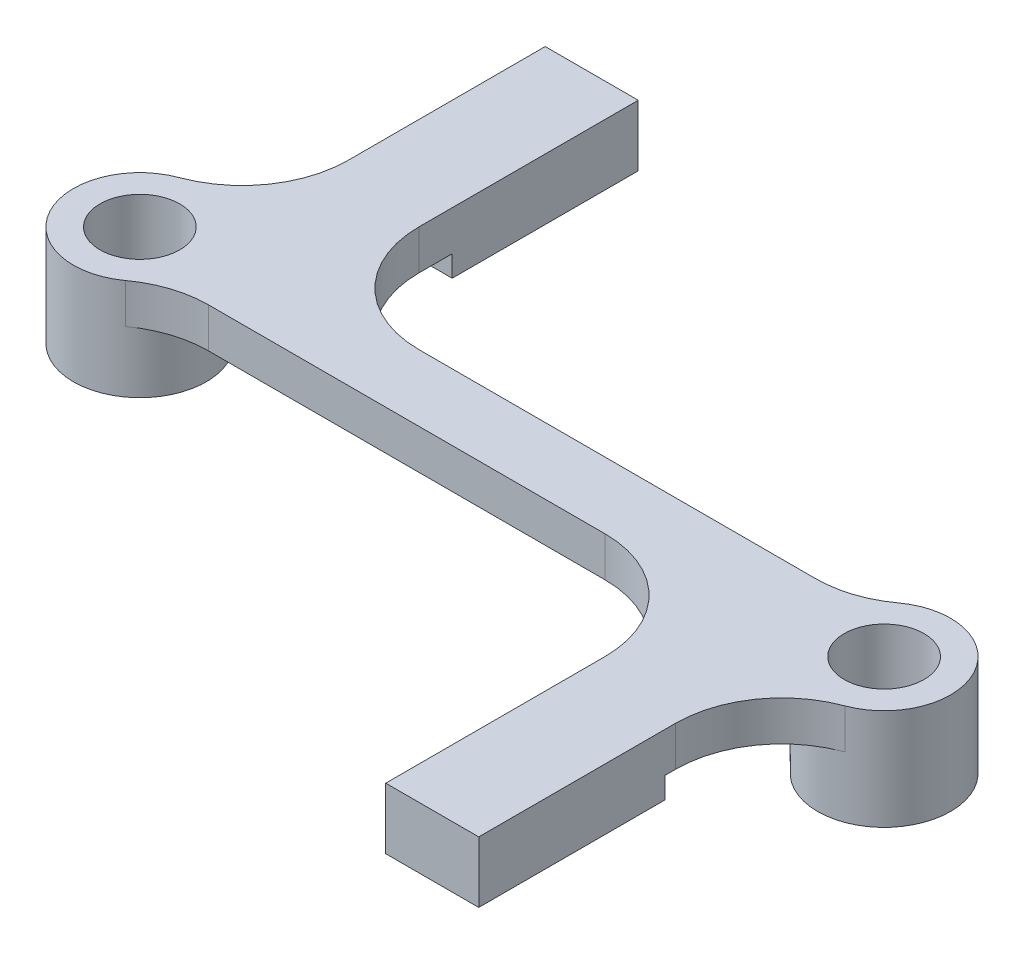
SolidWorks part; units mm, degrees
material "6061-T6 (SS)"
ref_plane "Front Plane" through (0, 0, 0) normal (0, 0, 1) x (1, 0, 0)
ref_plane "Top Plane" through (0, 0, 0) normal (0, 1, 0) x (1, 0, 0)
ref_plane "Right Plane" through (0, 0, 0) normal (1, 0, 0) x (0, 0, -1)
sketch "Sketch1" plane through (0, 0, 0) normal (0, 1, 0) x (1, 0, 0)
  line L0 (-14, 0) -> (14, 0) construction
  line L1 (0, 1.25) -> (0, 0) construction
  line L2 (-11.8349, 1.25) -> (11.8349, 1.25)
  line L3 (-11.8349, 1.25) -> (-11.8349, -1.25)
  line L4 (-11.8349, -1.25) -> (11.8349, -1.25)
  line L5 (11.8349, 1.25) -> (11.8349, -1.25)
  circle A0 centre (-14, 0) radius 1.5
  circle A1 centre (14, 0) radius 1.5
  circle A2 centre (-14, 0) radius 2.5
  circle A3 centre (14, 0) radius 2.5
  point P24 (-11.8349, 0)
  dimension "D2" = 2.5
  dimension "D3" = 5
  dimension "D4" = 3
  dimension "D1" = 28
extrude "Boss-Extrude2" add sketch "Sketch1" along normal blind 3.8 contours L3 A2 A0 | L3 A2 | A3 L2 A2 L4 | L5 A3 | L5 A3 A1 region at (-11.7002, 0, 0) region at (0, 0, 0) region at (-11.9033, 0, 0) region at (14.6293, 0, -2.3488) region at (11.7002, 0, 0)
sketch "Sketch2" plane through (0, 3.8, 0) normal (0, 1, 0) x (1, 0, 0)
  line L0 (-11.8349, 1.25) -> (11.8349, 1.25) construction
  line L1 (-12.25, 6.5) -> (-8.75, 6.5)
  line L2 (-12.25, 6.5) -> (-12.25, 13.5)
  line L3 (-12.25, 13.5) -> (-8.75, 13.5)
  line L4 (-8.75, 6.5) -> (-8.75, 13.5)
  line L5 (-12.25, 6.5) -> (-8.75, 6.5)
  line L6 (-12.25, 6.5) -> (-12.25, 1.25)
  line L7 (-12.25, 1.25) -> (-8.75, 1.25)
  line L8 (-8.75, 6.5) -> (-8.75, 1.25)
  line L9 (-11.8349, -1.25) -> (11.8349, -1.25) construction
  line L10 (8.75, -1.25) -> (12.25, -1.25)
  line L11 (8.75, -1.25) -> (8.75, -6.5)
  line L12 (8.75, -6.5) -> (12.25, -6.5)
  line L13 (12.25, -1.25) -> (12.25, -6.5)
  line L15 (8.75, -6.5) -> (12.25, -6.5)
  line L16 (8.75, -6.5) -> (8.75, -13.5)
  line L17 (8.75, -13.5) -> (12.25, -13.5)
  line L18 (12.25, -6.5) -> (12.25, -13.5)
  circle A0 centre (-14, 0) radius 1.5 construction
  circle A1 centre (14, 0) radius 1.5 construction
  arc M7 (-11.8349, 1.25) -> (-11.8349, -1.25) centre (-14, 0) ccw
  line M10 (11.8349, 1.25) -> (-11.8349, 1.25)
  dimension "D1" = 6.5
  dimension "D3" = 5.25
  dimension "D4" = 13.5
  dimension "D5" = 6.5
  dimension "D6" = 1.75
  dimension "D2" = 1.75
  dimension "D7" = 5.25
  dimension "D8" = 13.5
extrude "Boss-Extrude3" add sketch "Sketch2" against normal up to surface (3.8 mm away) contours L1 L4 L3 L2 | L8 L1 L6 M7 M10 | L11 L10 L13 L12 | L16 L15 L18 L17 region at (-10.5, 3.8, -10) region at (-10.4893, 3.8, -3.8912) up to face at (-14, 0, 1.5)
sketch "Sketch3" plane through (0, 0, 0) normal (0, -1, 0) x (1, 0, 0)
  line L0 (8.75, 6.5) -> (12.25, 6.5) construction
  line L1 (12.25, 1.25) -> (12.25, 6.5) construction
  line L2 (8.75, 1.25) -> (12.25, 1.25) construction
  line L3 (8.75, 1.25) -> (8.75, 6.5) construction
  line L4 (8.75, 6.5) -> (12.25, 6.5) construction
  line L5 (8.75, 6.5) -> (8.75, 13.5) construction
  line L6 (8.75, 13.5) -> (12.25, 13.5) construction
  line L7 (12.25, 6.5) -> (12.25, 13.5) construction
  line L8 (-12.25, -6.5) -> (-8.75, -6.5) construction
  line L9 (-12.25, -6.5) -> (-12.25, -13.5) construction
  line L10 (-12.25, -13.5) -> (-8.75, -13.5) construction
  line L11 (-8.75, -6.5) -> (-8.75, -13.5) construction
  line L12 (-12.25, -6.5) -> (-8.75, -6.5) construction
  line L13 (-12.25, -6.5) -> (-12.25, -1.25) construction
  line L14 (-12.25, -1.25) -> (-8.75, -1.25) construction
  line L15 (-8.75, -6.5) -> (-8.75, -1.25) construction
  line L16 (8.75, 6.5) -> (12.25, 6.5)
  line L17 (12.25, 1.25) -> (12.25, 6.5)
  line L18 (8.75, 1.25) -> (12.25, 1.25)
  line L19 (8.75, 1.25) -> (8.75, 6.5)
  line L20 (8.75, 6.5) -> (12.25, 6.5)
  line L21 (8.75, 6.5) -> (8.75, 13.5)
  line L22 (8.75, 13.5) -> (12.25, 13.5)
  line L23 (12.25, 6.5) -> (12.25, 13.5)
  line L24 (-12.25, -6.5) -> (-8.75, -6.5)
  line L25 (-12.25, -6.5) -> (-12.25, -13.5)
  line L26 (-12.25, -13.5) -> (-8.75, -13.5)
  line L27 (-8.75, -6.5) -> (-8.75, -13.5)
  line L28 (-12.25, -6.5) -> (-8.75, -6.5)
  line L29 (-12.25, -6.5) -> (-12.25, -1.25)
  line L30 (-12.25, -1.25) -> (-8.75, -1.25)
  line L31 (-8.75, -6.5) -> (-8.75, -1.25)
  line L32 (-8.75, -1.25) -> (11.8349, -1.25)
  line L33 (8.75, 1.25) -> (-11.8349, 1.25)
  circle A0 centre (14, 0) radius 2.5
  circle A1 centre (-14, 0) radius 2.5
  line M3 (12.25, 1.7854) -> (12.25, 13.5)
  line M5 (8.75, 13.5) -> (8.75, 1.25)
  line M6 (8.75, 1.25) -> (-11.8349, 1.25)
  line M8 (-12.25, -1.7854) -> (-12.25, -13.5)
  line M10 (-8.75, -13.5) -> (-8.75, -1.25)
  line M11 (-8.75, -1.25) -> (11.8349, -1.25)
extrude "Cut-Extrude1" cut sketch "Sketch3" against normal offset from surface (2.3 mm away) 1.5 contours A1 L30 A0 L18 M11 M6 | A0 L16 L18 M3 M5 | A1 L24 L30 M8 M10 region at (10.4893, 0, 3.8912) region at (0, 0, 0) region at (-10.4893, 0, -3.8912) up to face at (0, 3.8, 0)
sketch "Sketch4" plane through (0, 0, 0) normal (0, -1, 0) x (1, 0, 0)
  line L0 (-8.75, -13.5) -> (-8.75, -6.5) construction
  line L1 (-8.75, -6.5) -> (-12.25, -6.5) construction
  line L2 (-12.25, -6.5) -> (-12.25, -13.5) construction
  line L3 (-12.25, -13.5) -> (-8.75, -13.5) construction
  line L4 (8.75, 6.5) -> (12.25, 6.5) construction
  line L5 (12.25, 6.5) -> (12.25, 13.5) construction
  line L6 (12.25, 13.5) -> (8.75, 13.5) construction
  line L7 (8.75, 13.5) -> (8.75, 6.5) construction
  line L8 (-8.75, -13.5) -> (-8.75, -6.5)
  line L9 (-8.75, -6.5) -> (-12.25, -6.5)
  line L10 (-12.25, -6.5) -> (-12.25, -13.5)
  line L11 (-12.25, -13.5) -> (-8.75, -13.5)
  line L12 (8.75, 6.5) -> (12.25, 6.5)
  line L13 (12.25, 6.5) -> (12.25, 13.5)
  line L14 (12.25, 13.5) -> (8.75, 13.5)
  line L15 (8.75, 13.5) -> (8.75, 6.5)
extrude "Cut-Extrude2" cut sketch "Sketch4" against normal blind 1.5
fillet "Fillet1" radius 4 6 edges at (-8.75, 3.05, -1.25) (-12.25, 3.05, -1.7854) (-11.8349, 3.05, 1.25) (8.75, 3.05, 1.25) (12.25, 3.05, 1.7854) (11.8349, 3.05, -1.25)
